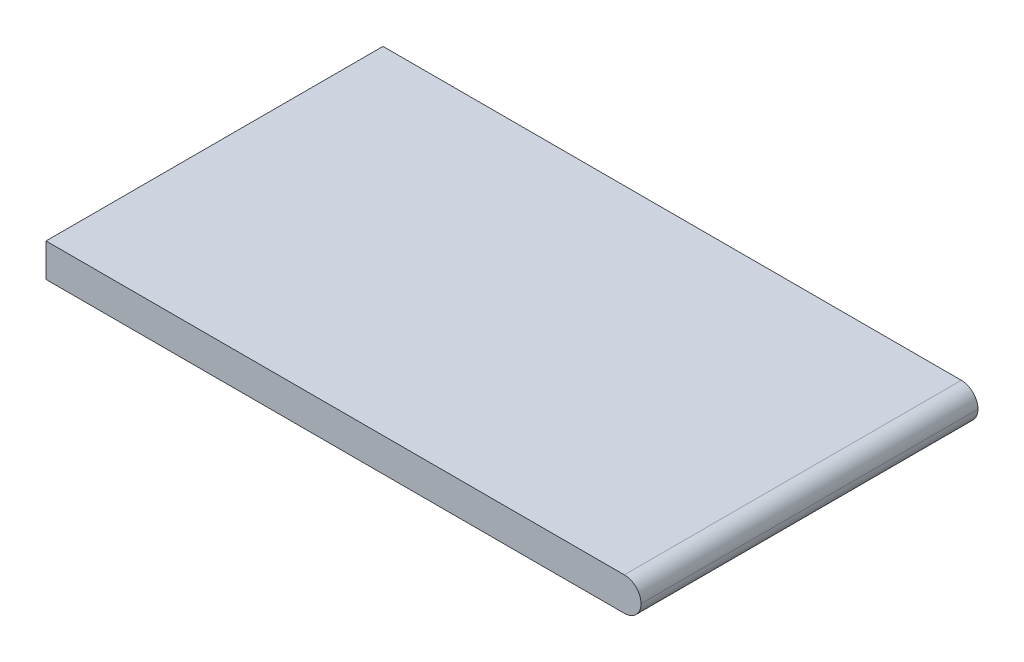
SolidWorks part; units mm, degrees
ref_plane "Front Plane" through (0, 0, 0) normal (0, 0, 1) x (1, 0, 0)
ref_plane "Top Plane" through (0, 0, 0) normal (0, 1, 0) x (1, 0, 0)
ref_plane "Right Plane" through (0, 0, 0) normal (1, 0, 0) x (0, 0, -1)
other "Center of Mass"
ref_plane "Plane2" through (0, 0, 30.3) normal (0, 0, 1) x (1, 0, 0)
sketch "Sketch1" plane through (0, 0, 0) normal (0, 0, 1) x (1, 0, 0)
  line L1 (-4.25, 1.5) -> (49.25, 1.5)
  line L2 (-4.25, 1.5) -> (-4.25, -1.5)
  line L3 (-4.25, -1.5) -> (49.25, -1.5)
  line L4 (49.25, 1.5) -> (49.25, -1.5)
  point P4 (49.25, 0)
  point P6 (0, 0)
  dimension "D1" = 53.5
  dimension "D2" = 4.25
  dimension "D3" = 3
extrude "Boss-Extrude1" add sketch "Sketch1" along normal up to surface (30.3 mm away) contours L4 L1 L3 | L2 L3 L1 region at (22.5, 0, 0) up to plane "Plane2"
fillet "Fillet1" radius 1.5 2 edges at (49.25, -1.5, 15.15) (49.25, 1.5, 15.15)
ref_axis "Axis1" through (0, 0, -7.6722) along (0, 0, 1)
